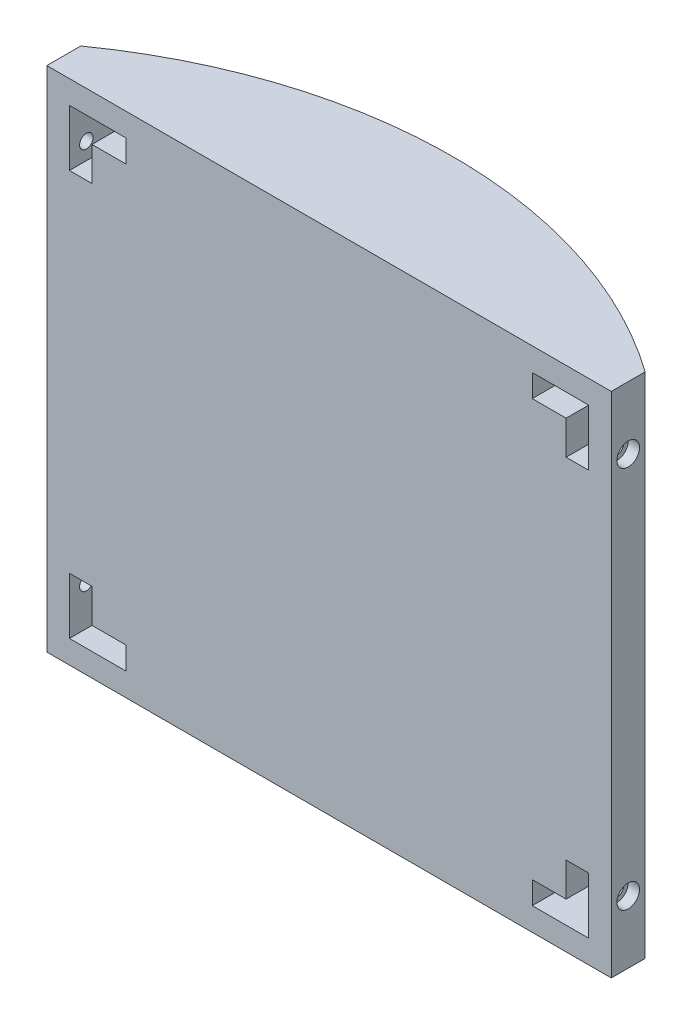
SolidWorks part; units mm, degrees
other "标注1"
sketch "草图3" plane through (-22.25, 4, -10) normal (-0.231, 0.6469, -0.7268) x (-0.9696, -0.2151, 0.1167)
ref_plane "前视基准面" through (0, 0, 0) normal (0, 0, 1) x (1, 0, 0)
ref_plane "上视基准面" through (0, 0, 0) normal (0, 1, 0) x (1, 0, 0)
ref_plane "右视基准面" through (0, 0, 0) normal (1, 0, 0) x (0, 0, -1)
other "Configuration Table"
sketch "草图4" plane through (0, 0, 0) normal (0, 1, 0) x (1, 0, 0)
  line L0 (-44.4144, 8) -> (57.5161, 8) construction
  line L7 (-25, 0) -> (25, 0) construction
  line L8 (-25, 0) -> (-25, -3)
  line L9 (-25, -3) -> (25, -3)
  line L10 (25, 0) -> (25, -3)
  arc A0 (-25, 0) -> (25, 0) centre (0, -35.0625) cw
  dimension "D1" = 3
  dimension "D2" = 50
  dimension "D3" = 8
extrude "凸台-拉伸1" add sketch "草图4" along normal blind 45
sketch "草图5" plane through (0, 0, 3) normal (0, 0, 1) x (1, 0, 0)
  line L0 (-25, 0) -> (25, 0) construction
  line L1 (-23, 42.95) -> (-18, 42.95)
  line L2 (-23, 42.95) -> (-23, 40.95)
  line L3 (-23, 40.95) -> (-18, 40.95)
  line L4 (-18, 42.95) -> (-18, 40.95)
  line L5 (-23, 42.95) -> (-21, 42.95)
  line L6 (-23, 42.95) -> (-23, 37.95)
  line L7 (-23, 37.95) -> (-21, 37.95)
  line L8 (-21, 42.95) -> (-21, 37.95)
  line L9 (23, 42.95) -> (21, 42.95)
  line L10 (23, 42.95) -> (23, 37.95)
  line L11 (23, 37.95) -> (21, 37.95)
  line L12 (21, 42.95) -> (21, 37.95)
  line L13 (23, 42.95) -> (18, 42.95)
  line L14 (23, 42.95) -> (23, 40.95)
  line L15 (23, 40.95) -> (18, 40.95)
  line L16 (18, 42.95) -> (18, 40.95)
  line L17 (-23, 2.05) -> (-21, 2.05)
  line L18 (-23, 2.05) -> (-23, 7.05)
  line L19 (-23, 7.05) -> (-21, 7.05)
  line L20 (-21, 2.05) -> (-21, 7.05)
  line L21 (-23, 2.05) -> (-18, 2.05)
  line L22 (-23, 2.05) -> (-23, 4.05)
  line L23 (-23, 4.05) -> (-18, 4.05)
  line L24 (-18, 2.05) -> (-18, 4.05)
  line L25 (23, 2.05) -> (21, 2.05)
  line L26 (23, 2.05) -> (23, 7.05)
  line L27 (23, 7.05) -> (21, 7.05)
  line L28 (21, 2.05) -> (21, 7.05)
  line L29 (23, 2.05) -> (18, 2.05)
  line L30 (23, 2.05) -> (23, 4.05)
  line L31 (23, 4.05) -> (18, 4.05)
  line L32 (18, 2.05) -> (18, 4.05)
  line L33 (-25, 45) -> (-25, 0) construction
  line L34 (-25, 45) -> (25, 45) construction
  line L35 (25, 45) -> (25, 0) construction
  point P36 (21, 7.05)
  point P37 (18, 40.45)
  dimension "D1" = 2.05
  dimension "D2" = 2
  dimension "D3" = 2.05
  dimension "D4" = 2
  dimension "D5" = 5
  dimension "D6" = 2
extrude "切除-拉伸1" cut sketch "草图5" against normal blind 4 contours L21 L24 L23 L22 | L17 L20 L19 L18 | L29 L32 L31 L30 | L25 L28 L27 L26 | L1 L4 L3 L2 | L5 L8 L7 L6 | L13 L16 L15 L14 | L10 L11 L12 L9
sketch "草图6" plane through (-25, 0, 0) normal (-1, 0, 0) x (0, 0, 1)
  line L0 (3, 45) -> (3, 0) construction
  line L1 (0, 0) -> (3, 0) construction
  line L2 (1.5, 5.55) -> (1.5, 0) construction
  line L3 (1.5, 39.45) -> (1.5, 45) construction
  line L4 (0, 45) -> (3, 45) construction
  circle A0 centre (1.5, 5.55) radius 1
  circle A1 centre (1.5, 5.55) radius 0.6
  circle A2 centre (1.5, 39.45) radius 1
  circle A3 centre (1.5, 39.45) radius 0.6
  point P10 (0, 0)
  dimension "D2" = 2
  dimension "D3" = 1.2
  dimension "D1" = 1.5
  dimension "D4" = 5.55
extrude "切除-拉伸2" cut sketch "草图6" against normal up to surface (2 mm away) contours A1 | A3 up to face at (-23, 4.55, 1)
extrude "切除-拉伸3" cut sketch "草图6<3>" against normal blind 1 contours A0 | A2
sketch "草图6<3>" plane through (-25, 0, 0) normal (-1, 0, 0) x (0, 0, 1) same geometry as "草图6"
extrude "切除-拉伸4" cut sketch "草图6<4>" along normal up to surface (-48 mm away) from surface contours A3 | A1 up to face at (23, 40.45, 1) starting at face at (25, 22.5, 1.5)
sketch "草图6<4>" plane through (-25, 0, 0) normal (-1, 0, 0) x (0, 0, 1) same geometry as "草图6"
extrude "切除-拉伸6" cut sketch "草图6<5>" along normal blind 1 from surface contours A2 | A0 starting at face at (25, 39.45, 2.1)
sketch "草图6<5>" plane through (-25, 0, 0) normal (-1, 0, 0) x (0, 0, 1) same geometry as "草图6"
